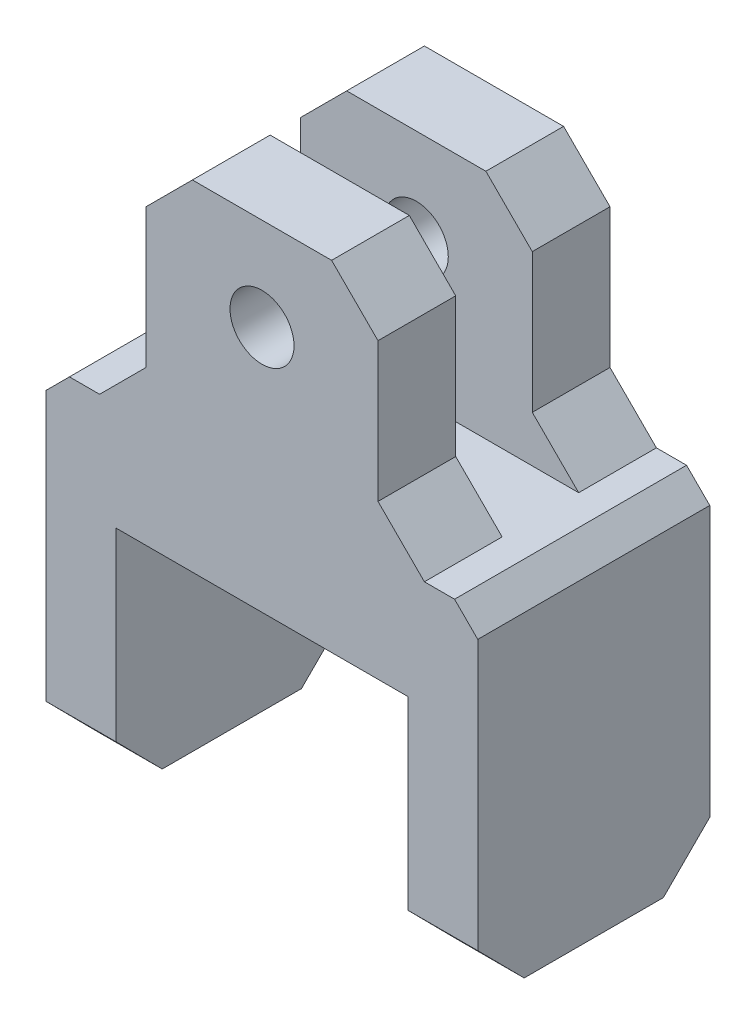
SolidWorks part; units mm, degrees
ref_plane "Front Plane" through (0, 0, 0) normal (0, 0, 1) x (1, 0, 0)
ref_plane "Top Plane" through (0, 0, 0) normal (0, 1, 0) x (1, 0, 0)
ref_plane "Right Plane" through (0, 0, 0) normal (1, 0, 0) x (0, 0, -1)
sketch "Sketch3" plane through (0, 0, 0) normal (0, 0, 1) x (1, 0, 0)
  line L0 (27.7555, 15.0291) -> (26.4555, 15.0291)
  line L1 (26.4555, 15.0291) -> (25.4555, 14.0291)
  line L2 (25.4555, 14.0291) -> (25.4555, 0.3891)
  line L3 (25.4555, 0.3891) -> (28.4555, 0.3891)
  line L4 (28.4555, 0.3891) -> (28.4555, 10.3891)
  line L5 (28.4555, 10.3891) -> (41.0555, 10.3891)
  line L6 (41.0555, 10.3891) -> (41.0555, 0.3891)
  line L7 (41.0555, 0.3891) -> (44.0555, 0.3891)
  line L8 (44.0555, 0.3891) -> (44.0555, 14.0291)
  line L9 (44.0555, 14.0291) -> (43.0555, 15.0291)
  line L10 (43.0555, 15.0291) -> (41.7555, 15.0291)
  line L11 (41.7555, 15.0291) -> (39.7555, 17.0291)
  line L13 (29.7555, 17.0291) -> (27.7555, 15.0291)
  line L14 (29.7555, 17.0291) -> (29.7555, 23.0291)
  line L15 (29.7555, 23.0291) -> (31.7555, 25.0291)
  line L16 (31.7555, 25.0291) -> (37.7555, 25.0291)
  line L17 (37.7555, 25.0291) -> (39.7555, 23.0291)
  line L18 (39.7555, 23.0291) -> (39.7555, 17.0291)
extrude "Boss-Extrude2" add sketch "Sketch3" along normal blind 5 and the other way blind 5
sketch "Sketch4" plane through (44.0555, 0, 0) normal (1, 0, 0) x (0, 0, -1)
  line L0 (-5, 0.3891) -> (-3, 0.3891)
  line L1 (5, 0.3891) -> (-5, 0.3891) construction
  line L2 (-5, 0.3891) -> (-5, 2.4108)
  line L3 (-5, 0.3891) -> (-5, 14.0291) construction
  line L4 (-5, 2.4108) -> (-3, 0.3891)
extrude "Cut-Extrude1" cut sketch "Sketch4" against normal up to vertex (18.6 mm away) up to point (25.4555, 0.3891, 5)
sketch "Sketch5" plane through (44.0555, 0, 0) normal (1, 0, 0) x (0, 0, -1)
  line L0 (5, 0.3891) -> (-3, 0.3891) construction
  line L1 (5, 0.3891) -> (3, 0.3891)
  line L2 (5, 0.3891) -> (5, 2.3891)
  line L3 (5, 0.3891) -> (5, 14.0291) construction
  line L4 (5, 2.3891) -> (3, 0.3891)
extrude "Cut-Extrude2" cut sketch "Sketch5" against normal up to vertex (18.6 mm away) up to point (25.4555, 0.3891, -5)
sketch "Sketch7" plane through (44.0555, 0, 0) normal (1, 0, 0) x (0, 0, -1)
  line L1 (5, 15.0291) -> (-5, 15.0291) construction
  line L2 (-1.65, 15.0291) -> (-1.65, 25.0291)
  line L3 (5, 25.0291) -> (-5, 25.0291) construction
  line L4 (-1.65, 25.0291) -> (1.65, 25.0291)
  line L5 (1.65, 25.0291) -> (1.65, 15.0291)
  line L6 (5, 15.0291) -> (-5, 15.0291) construction
  line L7 (1.65, 15.0291) -> (-1.65, 15.0291)
extrude "Cut-Extrude3" cut sketch "Sketch7" against normal up to vertex (18.6 mm away) up to point (25.4555, 14.0291, -5)
sketch "Sketch8" plane through (0, 0, 5) normal (0, 0, 1) x (1, 0, 0)
  circle A0 centre (34.7555, 21.0291) radius 1.38
extrude "Cut-Extrude4" cut sketch "Sketch8" against normal up to vertex (10 mm away) up to point (39.7555, 23.0291, -5)
